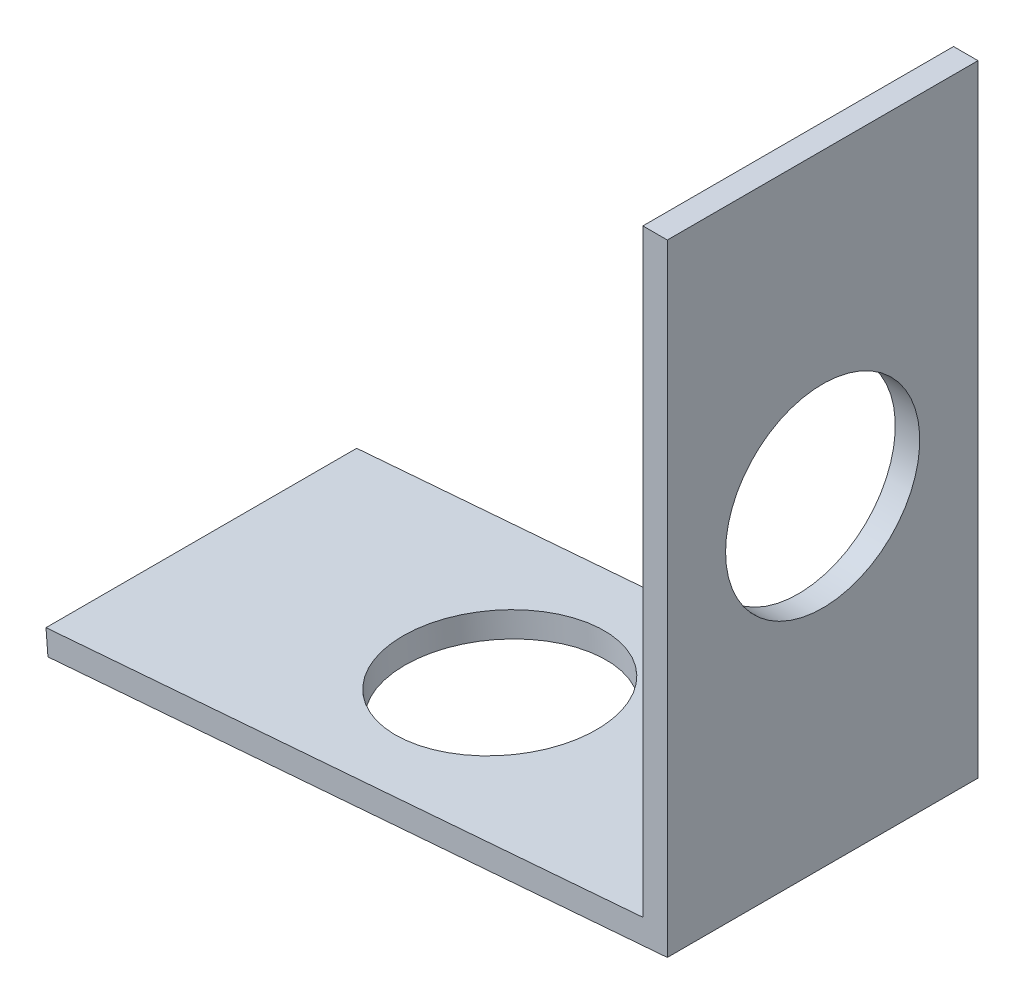
SolidWorks part; units mm, degrees
material "6061 Alloy"
ref_plane "Front Plane" through (0, 0, 0) normal (0, 0, 1) x (1, 0, 0)
ref_plane "Top Plane" through (0, 0, 0) normal (0, 1, 0) x (1, 0, 0)
ref_plane "Right Plane" through (0, 0, 0) normal (1, 0, 0) x (0, 0, -1)
sketch "Sketch1" plane through (0, 0, 0) normal (0, 0, 1) x (1, 0, 0)
  line L0 (0, 0) -> (0, 25.4)
  line L1 (0, 0) -> (-25.3196, -2.0194)
  line L2 (-1, 0.9234) -> (-25.3991, -1.0225)
  line L3 (-1, 0.9234) -> (-1, 25.4)
  line L4 (-25.3991, -1.0225) -> (-25.3196, -2.0194)
  line L5 (-1, 25.4) -> (0, 25.4)
  dimension "D1" = 25.4
  dimension "D2" = 94.56
  dimension "D3" = 25.4
  dimension "D4" = 1
extrude "Boss-Extrude1" add sketch "Sketch1" along normal mid plane 12.7
sketch "Sketch2" plane through (-1, 0, 0) normal (-1, 0, 0) x (0, 0, 1)
  line L0 (-6.35, 13.1617) -> (6.35, 13.1617) construction
  line L1 (-6.35, 25.4) -> (-6.35, 0.9234) construction
  line L2 (6.35, 25.4) -> (6.35, 0.9234) construction
  line L3 (0, 25.4) -> (0, 0.9234) construction
  line L4 (6.35, 25.4) -> (-6.35, 25.4) construction
  line L5 (6.35, 0.9234) -> (-6.35, 0.9234) construction
  point P12 (0, 13.1617)
hole_wizard "5/16 (0.3125) Diameter Hole1" positions "3DSketch1" profile "Sketch3" hole size "5/16" standard "ANSI Inch" end condition through all
sketch3d "3DSketch1"
  point P0 (-1, 13.1617, 0)
sketch "Sketch3" plane through (-1, 13.1617, 0) normal (0, 1, 0) x (0, 0, 1)
  line L0 (0, 0) -> (0, 1)
  line L1 (0, 1) -> (3.9688, 1)
  line L2 (3.9688, 1) -> (3.9687, 0)
  line L5 (3.9687, 0) -> (0, 0)
  line L11 (0, -6.35) -> (0, 107.95) construction
  dimension "Thru Hole Dia." = 7.9375
  dimension "Thru Hole Depth" = 1
sketch "Sketch4" plane through (-0.0795, 0.9968, 0) normal (-0.0795, 0.9968, 0) x (0.9968, 0.0795, 0)
  line L0 (-13.1617, 6.35) -> (-13.1617, -6.35) construction
  line L1 (-0.9234, 6.35) -> (-25.4, 6.35) construction
  line L2 (-0.9234, -6.35) -> (-25.4, -6.35) construction
  line L3 (-25.4, 0) -> (-0.9234, 0) construction
  line L4 (-25.4, -6.35) -> (-25.4, 6.35) construction
  line L5 (-0.9234, -6.35) -> (-0.9234, 6.35) construction
  point P12 (-13.1617, 0)
hole_wizard "5/16 (0.3125) Diameter Hole2" positions "3DSketch2" profile "Sketch5" hole size "5/16" standard "ANSI Inch" end condition through all
sketch3d "3DSketch2"
  point P0 (-13.1996, -0.0496, 0)
sketch "Sketch5" plane through (-13.1996, -0.0496, 0) normal (0, 0, 1) x (-0.9968, -0.0795, 0)
  line L0 (0, 0) -> (0, 3.013)
  line L1 (0, 3.013) -> (3.9688, 3.013)
  line L2 (3.9688, 3.013) -> (3.9687, 0)
  line L5 (3.9687, 0) -> (0, 0)
  line L11 (0, -6.35) -> (0, 107.95) construction
  dimension "Thru Hole Dia." = 7.9375
  dimension "Thru Hole Depth" = 3.013
